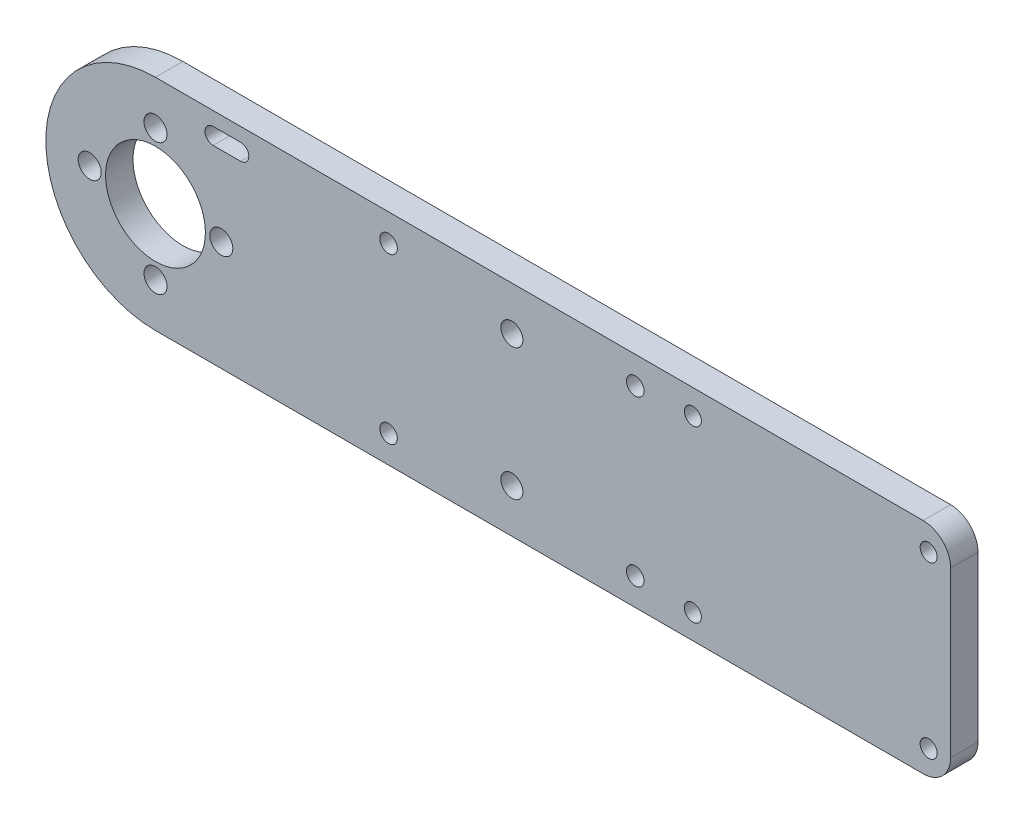
SolidWorks part; units mm, degrees
material "Acrylic (Medium-high impact)"
ref_plane "Front Plane" through (0, 0, 0) normal (0, 0, 1) x (1, 0, 0)
ref_plane "Top Plane" through (0, 0, 0) normal (0, 1, 0) x (1, 0, 0)
ref_plane "Right Plane" through (0, 0, 0) normal (1, 0, 0) x (0, 0, -1)
sketch "Sketch2" plane through (0, 0, 0) normal (0, 0, 1) x (1, 0, 0)
  line L0 (0, 20) -> (0, -20)
  line L1 (0, 20) -> (145, 20)
  line L2 (0, -20) -> (145, -20)
  line L3 (145, 20) -> (145, -20)
  line L4 (0, 0) -> (-20, 0)
  circle A0 centre (0, 0) radius 20
  circle A1 centre (0, 0) radius 9.1
  dimension "D1" = 40
  dimension "D3" = 18.2
  dimension "D2" = 165
extrude "Boss-Extrude1" add sketch "Sketch2" along normal mid plane 5 contours A1 L0 A0 | A0 L2 L3 L1 | A1 L4 A0 L0 | A1 L0 A0 L4 region at (9.696, 0, 0) region at (80.2769, 0, 0) region at (-9.696, 9.696, 0) region at (-9.696, -9.696, 0)
fillet "Fillet1" radius 5 2 edges at (145, -20, 0) (145, 20, 0)
sketch "Sketch3" plane through (0, 0, -2.5) normal (0, 0, -1) x (-1, 0, 0)
  line L0 (-119.5, 20) -> (-119.5, -20)
  line L1 (-119.5, 0) -> (-98, 0)
  line L2 (-98, 0) -> (-98, 15.5)
  line L3 (-145, 15) -> (-145, -15)
  line L4 (-140, -20) -> (0, -20)
  line L5 (0, 20) -> (-140, 20)
  line L6 (-145, 15) -> (-145, -15)
  line L7 (-140, -20) -> (0, -20)
  line L8 (0, 20) -> (-140, 20)
  line L9 (-119.5, 0) -> (-65, 0)
  line L10 (-65, 0) -> (-65, 15)
  line L11 (-65, 15) -> (-87.5, 15)
  line L12 (0, 0) -> (0, 12)
  line L13 (0, 0) -> (-65, 0)
  line L14 (-15.5185, 16) -> (-10.5185, 16) construction
  line L17 (-15.5185, 17.5) -> (-10.5185, 17.5)
  line L18 (-15.5185, 14.5) -> (-10.5185, 14.5)
  line L19 (0, 0) -> (18.4819, 0)
  line L20 (-65, 0.6163) -> (-65, 6.1951)
  line L21 (-65, 0) -> (-65, 12)
  circle A0 centre (0, 0) radius 12
  circle A1 centre (-98, 15.5) radius 1.55
  circle A2 centre (-98, -15.5) radius 1.55
  arc A3 (-145, -15) -> (-140, -20) centre (-140, -15) ccw
  arc A4 (0, -20) -> (0, 20) centre (0, 0) ccw
  arc A5 (-140, 20) -> (-145, 15) centre (-140, 15) ccw
  arc A6 (-145, -15) -> (-140, -20) centre (-140, -15) ccw
  arc A7 (0, -20) -> (0, 20) centre (0, 0) ccw
  arc A8 (-140, 20) -> (-145, 15) centre (-140, 15) ccw
  circle A9 centre (-141, -15.5) radius 1.55
  circle A10 centre (-141, 15.5) radius 1.55
  circle A11 centre (-87.5, 15) radius 1.6
  circle A12 centre (-87.5, -15) radius 1.6
  circle A13 centre (-42.5, -15) radius 1.6
  circle A14 centre (-42.5, 15) radius 1.6
  circle A15 centre (0, 12) radius 2.1
  circle A16 centre (12, 0) radius 2.1
  circle A17 centre (0, -12) radius 2.1
  circle A18 centre (-12, 0) radius 2.1
  arc A21 (-15.5185, 17.5) -> (-15.5185, 14.5) centre (-15.5185, 16) ccw
  arc A22 (-10.5185, 14.5) -> (-10.5185, 17.5) centre (-10.5185, 16) ccw
  circle A23 centre (-65, 12) radius 2
  circle A25 centre (-65, -12) radius 2
  point P35 (-13.0185, 16)
  point P48 (12, 0)
  point P53 (-12, 0)
  point P54 (0, -12)
  dimension "D2" = 24
  dimension "D6" = 3.1
  dimension "D10" = 3.2
  dimension "D11" = 4.2
  dimension "D13" = 65
  dimension "D17" = 65
  dimension "D18" = 4.2
  dimension "D12" = 4.2
  dimension "D19" = 4.2
  dimension "D21" = 4
  dimension "D3" = 21.5
  dimension "D4" = 15.5
  dimension "D5" = 98
  dimension "D7" = 27
  dimension "D8" = 15
  dimension "D9" = 22.5
  dimension "D14" = 5
  dimension "D15" = 3
  dimension "D16" = 4
  dimension "D20" = 12
  dimension "D1" = 0
extrude "Cut-Extrude1" cut sketch "Sketch3" against normal through all contours L19 A16 A0 | A0 A16 L19 | L19 A16 A0 | A0 A16 L19 | A0 A15 | A0 A15 L12 | L12 A15 A0 | A0 A18 L13 | L13 A18 A0 | A0 A18 L13 | L13 A18 A0 | A0 A17 | A0 A17 region at (12.8574, 0.9157, -2.5) region at (12.8574, -0.9157, -2.5) region at (11.0765, 0.8649, -2.5) region at (11.0765, -0.8649, -2.5) region at (0, 12.8574, -2.5) region at (0.8649, 11.0765, -2.5) region at (0, -11.0765, -2.5) region at (0, -12.8574, -2.5) region at (-0.8649, 11.0765, -2.5) region at (-11.0765, 0.8649, -2.5) region at (-11.0765, -0.8649, -2.5) region at (-12.8574, -0.9157, -2.5) region at (-12.8574, 0.9157, -2.5)
extrude "Cut-Extrude2" cut sketch "Sketch3<4>" against normal blind 10 contours L18 A22 L17 A21 | A12 | A11 | A13 | A14 | A10 | A9 | A1 | A2 | L21 A23 L10 | L10 A23 L21 | A25 region at (99.065, 16.565, -2.5) region at (89.0547, 15, -2.5) region at (65.8488, 12, -2.5) region at (64.1512, 12, -2.5) region at (13.0185, 16, -2.5) region at (98, -15.5, -2.5) region at (141, -15.5, -2.5) region at (141, 15.5, -2.5) region at (87.5, -15, -2.5) region at (42.5, -15, -2.5) region at (42.5, 15, -2.5) region at (65, -12, -2.5)
sketch "Sketch3<4>" plane through (0, 0, -2.5) normal (0, 0, -1) x (-1, 0, 0) same geometry as "Sketch3"
